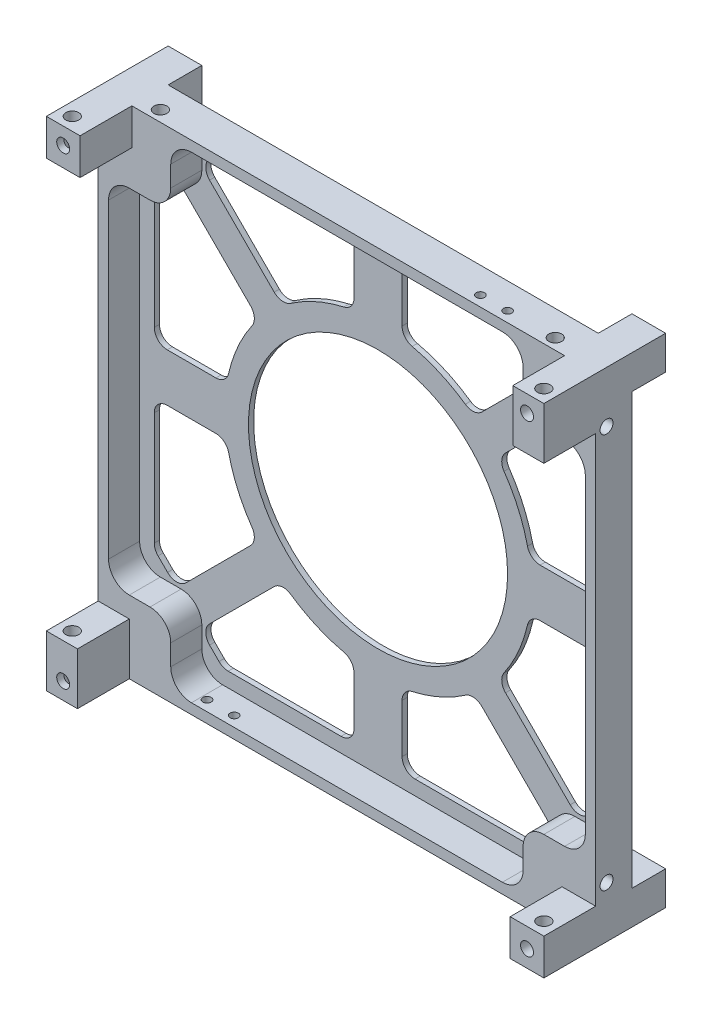
SolidWorks part; units mm, degrees
material "7075-T6 (SN)"
ref_plane "Front Plane" through (0, 0, 0) normal (0, 0, 1) x (1, 0, 0)
ref_plane "Top Plane" through (0, 0, 0) normal (0, 1, 0) x (1, 0, 0)
ref_plane "Right Plane" through (0, 0, 0) normal (1, 0, 0) x (0, 0, -1)
sketch "Sketch1" plane through (0, 0, 0) normal (0, 0, 1) x (1, 0, 0)
  line L0 (0, 0) -> (0, 62.6225) construction
  line L1 (-48, 48) -> (48, 48) construction
  line L2 (-48, 48) -> (-48, -48) construction
  line L3 (-48, -48) -> (48, -48) construction
  line L4 (48, 48) -> (48, -48) construction
  line L5 (0, 0) -> (75.6556, 0) construction
  point P4 (0, 48)
  point P5 (-48, 0)
  dimension "D1" = 96
  dimension "D2" = 96
sketch "Sketch2" plane through (0, 0, 0) normal (0, 0, 1) x (1, 0, 0)
  line L1 (48, 48) -> (41.5, 48)
  line L2 (48, 48) -> (48, 41.5)
  line L3 (48, 41.5) -> (41.5, 41.5)
  line L4 (41.5, 48) -> (41.5, 41.5)
  line L5 (48, -48) -> (41.5, -48)
  line L6 (48, -48) -> (48, -41.5)
  line L7 (48, -41.5) -> (41.5, -41.5)
  line L8 (41.5, -48) -> (41.5, -41.5)
  line L9 (-48, -48) -> (-41.5, -48)
  line L10 (-48, -48) -> (-48, -41.5)
  line L11 (-48, -41.5) -> (-41.5, -41.5)
  line L12 (-41.5, -48) -> (-41.5, -41.5)
  line L13 (-48, 48) -> (-41.5, 48)
  line L14 (-48, 48) -> (-48, 41.5)
  line L15 (-48, 41.5) -> (-41.5, 41.5)
  line L16 (-41.5, 48) -> (-41.5, 41.5)
  dimension "D1" = 6.5
  dimension "D2" = 6.5
  dimension "D3" = 6.5
  dimension "D4" = 6.5
  dimension "D5" = 6.5
  dimension "D6" = 6.5
  dimension "D7" = 6.5
  dimension "D8" = 6.5
sketch "Sketch3" plane through (0, 0, 0) normal (0, 0, 1) x (1, 0, 0)
  line L0 (48, 48) -> (0, 48)
  line L8 (48, 48) -> (48, -48) construction
  line L9 (48, 0) -> (48, 48)
  line L10 (4.64, 40.68) -> (4.64, 31.2753)
  line L12 (0, 0) -> (48, 48) construction
  line L13 (32.5122, 40.6157) -> (30.6801, 42.4478)
  line L14 (25, 0) -> (48, 0)
  line L15 (0, -200000) -> (0, 200062.6225) construction
  line L17 (-48, 48) -> (48, 48) construction
  line L21 (0, 25) -> (0, 48)
  line L22 (20.0352, 24.6032) -> (32.5122, 37.0801)
  line L23 (24.6032, 20.0352) -> (37.0801, 32.5122)
  line L24 (40.6157, 32.5122) -> (42.4478, 30.6801)
  line L25 (7.14, 43.18) -> (28.9124, 43.18)
  line L26 (43.18, 7.14) -> (43.18, 28.9124)
  line L27 (40.68, 4.64) -> (31.2753, 4.64)
  arc A0 (25, 0) -> (0, 25) centre (0, 0) ccw
  arc A1 (28.838, 6.5836) -> (24.3158, 16.8439) centre (0, 0) ccw
  arc A2 (16.8439, 24.3158) -> (6.5836, 28.838) centre (0, 0) ccw
  arc A3 (7.14, 43.18) -> (4.64, 40.68) centre (7.14, 40.68) ccw
  arc A4 (4.64, 31.2753) -> (6.5836, 28.838) centre (7.14, 31.2753) ccw
  arc A5 (20.0352, 24.6032) -> (16.8439, 24.3158) centre (18.2675, 26.3709) cw
  arc A6 (32.5122, 37.0801) -> (32.5122, 40.6157) centre (30.7445, 38.8479) ccw
  arc A7 (28.9124, 43.18) -> (30.6801, 42.4478) centre (28.9124, 40.68) cw
  arc A8 (31.2753, 4.64) -> (28.838, 6.5836) centre (31.2753, 7.14) cw
  arc A9 (40.68, 4.64) -> (43.18, 7.14) centre (40.68, 7.14) ccw
  arc A10 (43.18, 28.9124) -> (42.4478, 30.6801) centre (40.68, 28.9124) ccw
  arc A11 (24.6032, 20.0352) -> (24.3158, 16.8439) centre (26.3709, 18.2675) ccw
  arc A12 (37.0801, 32.5122) -> (40.6157, 32.5122) centre (38.8479, 30.7445) cw
  point P39 (4.64, 29.2138)
  point P42 (18.5072, 23.0751)
  point P45 (34.28, 38.8479)
  dimension "D1" = 50
  dimension "D2" = 4.58
  dimension "D10" = 2.5
  dimension "D11" = 2.5
  dimension "D3" = 4.64
  dimension "D4" = 4.82
  dimension "D5" = 6.46
  dimension "D6" = 3.23
  dimension "D7" = 4.82
  dimension "D8" = 4.64
  dimension "D9" = 13.72
extrude "Boss-Extrude2" add sketch "Sketch3" along normal blind 1
ref_axis "Axis1" through (0, 0, 7.875) along (0, 0, -1)
pattern_circular "CirPattern3" count 4 over 360 about axis through (0, 0, 7.875) along (0, 0, -1) of "Boss-Extrude2"
extrude "Boss-Extrude3" add sketch "Sketch2" against normal blind 6.5
sketch "Sketch4" plane through (0, 0, 1) normal (0, 0, 1) x (1, 0, 0)
  line L0 (46, -34) -> (46, 34)
  line L1 (34, 46) -> (-34, 46)
  line L2 (-46, 34) -> (-46, -34)
  line L3 (-34, -46) -> (34, -46)
  line L4 (-48, 48) -> (-48, -48)
  line L5 (-48, -48) -> (48, -48)
  line L6 (48, -48) -> (48, 48)
  line L7 (48, 48) -> (-48, 48)
  line L15 (-46, 34) -> (-34, 34)
  line L16 (-34, 46) -> (-34, 34)
  line L19 (46, 34) -> (34, 34)
  line L20 (34, 46) -> (34, 34)
  line L23 (46, -34) -> (34, -34)
  line L24 (34, -46) -> (34, -34)
  line L27 (-46, -34) -> (-34, -34)
  line L28 (-34, -46) -> (-34, -34)
  line L29 (-34, 46) -> (-46, 34) construction
  point P2 (46, -46)
  point P4 (46, 46)
  point P6 (-46, 46)
  point P7 (-46, -46)
  dimension "D3" = 14
  dimension "D4" = 14
  dimension "D5" = 2
  dimension "D6" = 2
  dimension "D1" = 14
  dimension "D2" = 14
  dimension "D7" = 2
  dimension "D8" = 2
extrude "Boss-Extrude4" add sketch "Sketch4" along normal blind 6
sketch "Sketch5" plane through (0, 0, 7) normal (0, 0, 1) x (1, 0, 0)
  line L1 (-48, 48) -> (-41.5, 48)
  line L2 (-48, 48) -> (-48, 41)
  line L3 (-48, 41) -> (-41.5, 41)
  line L4 (-41.5, 48) -> (-41.5, 41)
  line L5 (48, 48) -> (42, 48)
  line L6 (48, 48) -> (48, 38)
  line L7 (48, 38) -> (42, 38)
  line L8 (42, 48) -> (42, 38)
  line L9 (-48, -48) -> (-42, -48)
  line L10 (-48, -48) -> (-48, -38)
  line L11 (-48, -38) -> (-42, -38)
  line L12 (-42, -48) -> (-42, -38)
  line L13 (48, -48) -> (41.5, -48)
  line L14 (48, -48) -> (48, -41)
  line L15 (48, -41) -> (41.5, -41)
  line L16 (41.5, -48) -> (41.5, -41)
  dimension "D1" = 6.5
  dimension "D2" = 7
  dimension "D3" = 6
  dimension "D4" = 10
  dimension "D5" = 6.5
  dimension "D6" = 7
  dimension "D7" = 10
  dimension "D8" = 6
extrude "Boss-Extrude5" add sketch "Sketch5" along normal blind 10
sketch "RailHolePosition" plane through (0, 48, 0) normal (0, 1, 0) x (1, 0, 0)
  line L0 (45.5, 6.5) -> (45.5, -14.5) construction
  line L1 (48, -17) -> (48, 6.5) construction
  line L5 (-45.5, 6.5) -> (-45.5, -14.5) construction
  line L7 (48, 6.5) -> (41.5, 6.5) construction
  line L8 (-48, -17) -> (-48, 6.5) construction
  line L9 (-41.5, 6.5) -> (-48, 6.5) construction
  dimension "D1" = 21
  dimension "D2" = 2.5
  dimension "D3" = 2.5
hole_wizard "M3 Tapped RailHoles" positions "Sketch12" profile "Sketch13" tap size "M3" standard "ISO"
sketch "Sketch12" plane through (0, 48, 0) normal (0, 1, 0) x (1, 0, 0)
  point P8 (45.5, -14.5)
  point P11 (-45.5, -14.5)
sketch "Sketch13" plane through (45.5, 48, 14.5) normal (1, 0, 0) x (0, 0, 1)
  line L0 (0, 0) -> (0, 13.2511)
  line L1 (0, 13.2511) -> (1.25, 12.5)
  line L2 (1.25, 12.5) -> (1.25, 0)
  line L5 (1.25, 0) -> (0, 0)
  line L10 (0, 13.2511) -> (-1.25, 12.5) construction
  line L11 (0, -6.35) -> (0, 107.95) construction
  dimension "Tap Drill Dia." = 2.5
  dimension "Tap Drill Depth" = 12.5
  dimension "Drill Angle" = 118
cosmetic thread "Hole Thread1" parameters "D1"=7, "D2"=3
cosmetic thread "Hole Thread18" parameters "D1"=10, "D2"=3
mirror "RailHoles" about plane through (0, 0, 0) normal (0, 1, 0) of "M3 Tapped RailHoles"
cosmetic thread "Hole Thread19" parameters "D1"=7, "D2"=3
cosmetic thread "Hole Thread20" parameters "D1"=10, "D2"=3
sketch3d "SidePlateHole Positions"
  line L0 (-38.1, -48, 7) -> (-38.1, -48, 0) construction
  line L1 (-42, -48, 7) -> (41.5, -48, 7) construction
  line L2 (-48, -48, 0) -> (48, -48, 0) construction
  line L3 (-38.1, -48, 4.9) -> (-48, -48, 4.9) construction
  line L5 (-48, -48, 17) -> (-48, -48, -6.5) construction
  line L6 (-41.5, -48, 0) -> (41.5, -48, 0) construction
  line L17 (-48, -48, 4.9) -> (-48, -38.1, 4.9) construction
  line L18 (-48, -38.1, 4.9) -> (-48, -38.1, 0) construction
  line L19 (-48, 48, 0) -> (-48, -48, 0) construction
  dimension "D1" = 4.9
  dimension "D2" = 9.9
  dimension "D7" = 9.9
hole_wizard "M3x0.5 Tapped SidePlate" positions "Sketch16" profile "Sketch17" tap size "M3x0.5" standard "ANSI Metric"
sketch "Sketch16" plane through (0, -48, 0) normal (0, -1, 0) x (-1, 0, 0)
  point P0 (38.1, -4.9)
sketch "Sketch17" plane through (-38.1, -48, 4.9) normal (1, 0, 0) x (0, 0, -1)
  line L0 (0, 0) -> (0, 8.2511)
  line L1 (0, 8.2511) -> (1.25, 7.5)
  line L2 (1.25, 7.5) -> (1.25, 0)
  line L5 (1.25, 0) -> (0, 0)
  line L10 (0, 8.2511) -> (-1.25, 7.5) construction
  line L11 (0, -6.35) -> (0, 107.95) construction
  dimension "Tap Drill Dia." = 2.5
  dimension "Tap Drill Depth" = 7.5
  dimension "Drill Angle" = 118
cosmetic thread "Hole Thread3" parameters "D1"=6, "D2"=3
hole_wizard "M3x0.5 Tapped SidePlate2" positions "Sketch18" profile "Sketch19" tap size "M3x0.5" standard "ANSI Metric"
sketch "Sketch18" plane through (-48, 0, 0) normal (-1, 0, 0) x (0, 0, 1)
  point P0 (4.9, -38.1)
sketch "Sketch19" plane through (-48, -38.1, 4.9) normal (0, 1, 0) x (0, 0, 1)
  line L0 (0, 0) -> (0, 8.2511)
  line L1 (0, 8.2511) -> (1.25, 7.5)
  line L2 (1.25, 7.5) -> (1.25, 0)
  line L5 (1.25, 0) -> (0, 0)
  line L10 (0, 8.2511) -> (-1.25, 7.5) construction
  line L11 (0, -6.35) -> (0, 107.95) construction
  dimension "Tap Drill Dia." = 2.5
  dimension "Tap Drill Depth" = 7.5
  dimension "Drill Angle" = 118
cosmetic thread "Hole Thread4" parameters "D1"=6, "D2"=3
pattern_circular "SidePlateHoles" count 4 over 360 about axis through (0, 0, 1) along (0, 0, -1) of "M3x0.5 Tapped SidePlate", "M3x0.5 Tapped SidePlate2"
cosmetic thread "Hole Thread5" parameters "D1"=6, "D2"=3
cosmetic thread "Hole Thread6" parameters "D1"=6, "D2"=3
cosmetic thread "Hole Thread7" parameters "D1"=6, "D2"=3
cosmetic thread "Hole Thread8" parameters "D1"=6, "D2"=3
cosmetic thread "Hole Thread9" parameters "D1"=6, "D2"=3
cosmetic thread "Hole Thread10" parameters "D1"=6, "D2"=3
sketch3d "LimitSwitchHolePositions"
  line L0 (-48, -48, 5) -> (-29, -48, 5) construction
  line L1 (-48, -48, 17) -> (-48, -48, -6.5) construction
  line L2 (-48, -48, 0) -> (48, -48, 0) construction
  line L3 (-29, -48, 5) -> (-23.75, -48, 5) construction
  dimension "D1" = 19
  dimension "D2" = 5
  dimension "D3" = 5.25
hole_wizard "M2x0.4 Tapped Hole1" positions "Sketch20" profile "Sketch21" tap size "M2x0.4" standard "ANSI Metric"
sketch "Sketch20" plane through (0, -48, 0) normal (0, -1, 0) x (-1, 0, 0)
  point P0 (29, -5)
  point P3 (23.75, -5)
sketch "Sketch21" plane through (-29, -48, 5) normal (1, 0, 0) x (0, 0, -1)
  line L0 (0, 0) -> (0, 5.6807)
  line L1 (0, 5.6807) -> (0.8, 5.2)
  line L2 (0.8, 5.2) -> (0.8, 0)
  line L5 (0.8, 0) -> (0, 0)
  line L10 (0, 5.6807) -> (-0.8, 5.2) construction
  line L11 (0, -6.35) -> (0, 107.95) construction
  dimension "Tap Drill Dia." = 1.6
  dimension "Tap Drill Depth" = 5.2
  dimension "Drill Angle" = 118
cosmetic thread "Hole Thread11" parameters "D1"=4, "D2"=2
cosmetic thread "Hole Thread12" parameters "D1"=4, "D2"=2
pattern_circular "LimitSwitchHoles" count 2 over 360 about axis through (0, 0, 1) along (0, 0, -1) of "M2x0.4 Tapped Hole1"
cosmetic thread "Hole Thread13" parameters "D1"=4, "D2"=2
cosmetic thread "Hole Thread14" parameters "D1"=4, "D2"=2
fillet "Fillet2" radius 4 12 edges at (-46, -34, 4) (-34, -34, 4) (-34, -46, 4) (34, -46, 4) (34, -34, 4) (46, -34, 4) (46, 34, 4) (34, 34, 4) (34, 46, 4) (-34, 46, 4) (-34, 34, 4) (-46, 34, 4)
sketch "Sketch22" plane through (0, 0, 17) normal (0, 0, 1) x (1, 0, 0)
  line L0 (44.75, 48) -> (44.75, 44.75) construction
  line L1 (48, 48) -> (42, 48) construction
  line L3 (48, 38) -> (48, 48) construction
  dimension "D1" = 3.25
  dimension "D2" = 3.25
hole_wizard "M3 Tapped Standoff Hole" positions "Sketch23" profile "Sketch25" tap size "M3" standard "ISO" end condition through all
sketch "Sketch23" plane through (0, 0, 17) normal (0, 0, 1) x (1, 0, 0)
  point P0 (44.75, 44.75)
sketch "Sketch25" plane through (44.75, 44.75, 17) normal (1, 0, 0) x (0, -1, 0)
  line L0 (0, 0) -> (0, 23.5)
  line L1 (0, 23.5) -> (1.25, 23.5)
  line L2 (1.25, 23.5) -> (1.25, 0)
  line L5 (1.25, 0) -> (0, 0)
  line L11 (0, -6.35) -> (0, 107.95) construction
  dimension "Thread Major Dia." = 2.5
  dimension "Thru Tap Drill Depth" = 23.5
pattern_circular "StandoffHoles" count 4 over 360 about axis through (0, 0, 1) along (0, 0, -1) of "M3 Tapped Standoff Hole"
sketch "Sketch26" plane through (0, 0, 0) normal (0, 0, -1) x (-1, 0, 0)
  line L0 (0, 0) -> (40, -37.5) construction
  line L1 (0, -200000) -> (0, 200062.6225) construction
  line L2 (200000, 0) -> (-200075.6556, 0) construction
  line L3 (12.925, 0) -> (-12.925, 0) construction
  line L4 (0, 0) -> (40, 37.5) construction
  circle A0 centre (40, -37.5) radius 1.7
  circle A1 centre (40, 37.5) radius 1.7
  dimension "D3" = 3.4
  dimension "D1" = 40
  dimension "D2" = 37.5
extrude "Boss-Extrude6" add sketch "Sketch26" along normal blind 3
sketch "BottomHolePositions" plane through (0, 0, -3) normal (0, 0, -1) x (-1, 0, 0)
  line L0 (41.7, -37.5) -> (40, -37.5) construction
  line L1 (41.7, 37.5) -> (40, 37.5) construction
  circle A0 centre (40, -37.5) radius 1.7 construction
  circle A1 centre (40, 37.5) radius 1.7 construction
hole_wizard "M1.6x0.35 Tapped Hole1" positions "Sketch30" profile "Sketch31" tap size "M1.6x0.35" standard "ANSI Metric"
sketch "Sketch30" plane through (0, 0, -3) normal (0, 0, -1) x (-1, 0, 0)
  point P0 (40, -37.5)
  point P3 (40, 37.5)
sketch "Sketch31" plane through (-40, -37.5, -3) normal (1, 0, 0) x (0, 1, 0)
  line L0 (0, 0) -> (0, 3.3755)
  line L1 (0, 3.3755) -> (0.625, 3)
  line L2 (0.625, 3) -> (0.625, 0)
  line L5 (0.625, 0) -> (0, 0)
  line L10 (0, 3.3755) -> (-0.625, 3) construction
  line L11 (0, -6.35) -> (0, 107.95) construction
  dimension "Tap Drill Dia." = 1.25
  dimension "Tap Drill Depth" = 3
  dimension "Drill Angle" = 118
mirror "BottomHoles" about plane through (0, 0, 0) normal (1, 0, 0) of "Boss-Extrude6", "M1.6x0.35 Tapped Hole1"
